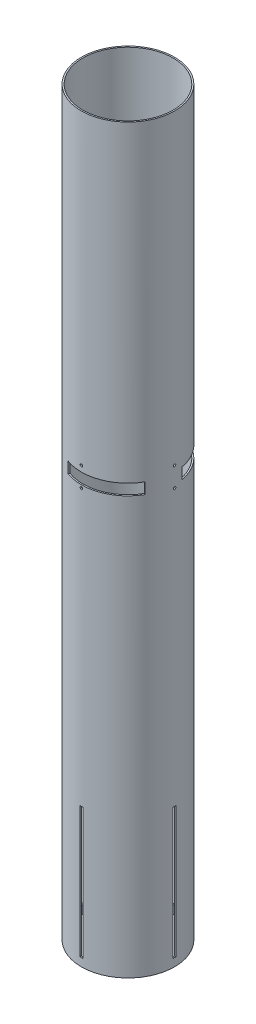
SolidWorks part; units mm, degrees
material "A-Glass Fiber"
ref_plane "Front Plane" through (0, 0, 0) normal (0, 0, 1) x (1, 0, 0)
ref_plane "Top Plane" through (0, 0, 0) normal (0, 1, 0) x (1, 0, 0)
ref_plane "Right Plane" through (0, 0, 0) normal (1, 0, 0) x (0, 0, -1)
sketch "Sketch1" plane through (0, 0, 0) normal (0, 1, 0) x (1, 0, 0)
  circle A0 centre (0, 0) radius 49.53
  circle A1 centre (0, 0) radius 51.1048
  dimension "D1" = 99.06
  dimension "D2" = 102.2096
extrude "Boss-Extrude1" add sketch "Sketch1" along normal blind 812.8
ref_plane "Plane1" through (0, 0, 0) normal (0.7071, 0, 0.7071) x (0.7071, 0, -0.7071)
ref_axis "Axis1" through (0, 812.8, 0) along (0, -1, 0)
sketch "Sketch2" plane through (0, 0, 0) normal (1, 0, 0) x (0, 0, -1)
  line L0 (0, 0) -> (0, 8.89)
  line L1 (1.5875, 8.89) -> (-1.5875, 8.89)
  line L2 (1.5875, 8.89) -> (1.5875, 152.4)
  line L3 (1.5875, 152.4) -> (-1.5875, 152.4)
  line L4 (-1.5875, 8.89) -> (-1.5875, 152.4)
  line L5 (1.5875, 8.89) -> (-1.5875, 152.4) construction
  line L6 (1.5875, 152.4) -> (-1.5875, 8.89) construction
  line L7 (51.1048, 812.8) -> (-51.1048, 812.8) construction
  line L8 (51.1048, 812.8) -> (-51.1048, 812.8)
  line L9 (0, 812.8) -> (0, 476.25)
  line L10 (-51.1048, 0) -> (51.1048, 0) construction
  circle A0 centre (0, 476.25) radius 1.3525
  point P0 (0, 80.645)
  dimension "D4" = 2.7051
  dimension "D1" = 3.175
  dimension "D5" = 476.25
  dimension "D3" = 152.4
  dimension "D2" = 8.89
extrude "Cut-Extrude1" cut sketch "Sketch2" against normal through all contours L4 L1 L2 L3 region at (0, 80.645, 0)
pattern_circular "CirPattern1" count 4 over 360 about axis through (0, 0, 0) along (0, 1, 0) of "Cut-Extrude1" reverse direction yes
extrude "Cut-Extrude2" cut sketch "Sketch2<3>" against normal through all contours A0 region at (0, 475.3207, 0.9293)
sketch "Sketch2<3>" plane through (0, 0, 0) normal (1, 0, 0) x (0, 0, -1) same geometry as "Sketch2"
pattern_circular "CirPattern2" count 4 over 360 about axis through (0, 812.8, 0) along (0, -1, 0) of "Cut-Extrude2"
sketch "Sketch3" plane through (0, 0, 0) normal (0.7071, 0, 0.7071) x (0.7071, 0, -0.7071)
  line L0 (0, 0) -> (0, 127) construction
  circle A0 centre (0, 127) radius 3.175
  dimension "D1" = 6.35
  dimension "D2" = 127
extrude "Cut-Extrude3" cut sketch "Sketch3" against normal through all
ref_plane "Plane3" through (0, 469.9, 0) normal (0, 1, 0) x (1, 0, 0)
sketch "Sketch7" plane through (0, 469.9, 0) normal (0, 1, 0) x (1, 0, 0)
  line L0 (0, 0) -> (-44.2581, -25.5524)
  line L1 (0, 0) -> (0, 93.232) construction
  line L2 (0, 0) -> (-32.8495, 39.1485)
  line L3 (-51.1048, 0) -> (0, 0) construction
  arc A0 (-51.0869, 1.3525) -> (-51.0869, -1.3525) centre (0, 0) ccw construction
  circle A1 centre (0, 0) radius 49.53 construction
  circle A2 centre (0, 0) radius 51.1048
  circle A3 centre (0, 0) radius 51.1048
  circle A4 centre (0, 0) radius 49.53
  circle A5 centre (0, 0) radius 51.1048 construction
  arc A6 (1.3526, 51.0869) -> (-1.3525, 51.0869) centre (0, 0) ccw construction
  arc A7 (-51.0869, 1.3525) -> (-51.0869, -1.3525) centre (0, 0) ccw
  arc A8 (1.3526, 51.0869) -> (-1.3525, 51.0869) centre (0, 0) ccw
  dimension "D1" = 80
  dimension "D3" = 30
  dimension "D2" = 0
extrude "Cut-Extrude4" cut sketch "Sketch7" against normal blind 12.065 contours A4 A3 L0 region at (-43.9137, 469.9, 24.5741)
pattern_circular "CirPattern3" count 3 over 360 about axis through (0, 812.8, 0) along (0, -1, 0) of "Cut-Extrude4"
pattern_linear "LPattern1" count 2 spacing 21.6916 along (0, -1, 0) of "CirPattern2"
equation "\"D1@Boss-Extrude1\" = \"Aft_Section_Length\""
equation "\"AB_Coupler_OD_Length\"= 1in"
equation "\"AB_Coupling_Section_Length\"= 0.375in"
equation "\"AB_Coupler_Length\"= \"AB_Coupler_OD_Length\" + \"AB_Coupling_Section_Length\" * 2"
equation "\"AB_Coupler_Num_Screws\"= 4"
equation "\"AB_Coupling_Screw_Diameter\"= 0.1065in"
equation "\"Aft_Section_Length\" = 32in"
equation "\"D4@Sketch2\"=\"AB_Coupling_Screw_Diameter\""
equation "\"D1@CirPattern2\"=\"AB_Coupler_Num_Screws\""
equation "\"Rail_Nut_From_Bottom\"= 5in"
equation "\"Rail_Nut_Diam\"= 0.25in"
equation "\"D1@Sketch3\"=\"Rail_Nut_Diam\""
equation "\"D2@Sketch3\"=\"Rail_Nut_From_Bottom\""
equation "\"AB_BKHD_Thickness\"= 0.375in"
equation "\"AB_Mount_From_Bottom\"= 18.75in"
equation "\"Cutout_Angle\" = 60"
equation "\"Motor_OD\" = 54.4mm"
equation "\"Motor_Length\" = 401mm"
equation "\"Mid_Coupler_Length\" = 12in"
equation "\"AB_Paddle_Height\" = 0.375in"
equation "\"Num_Cutouts\" = 4"
equation "\"AB_Coupler_OD\"= 4.024in"
equation "\"AB_Coupler_ID\"= 3.7in"
equation "\"AB_Coupler_Surface_Diameter\"= 3.899in"
equation "\"AB_Central_Bushing_Length\" = 0.75in"
equation "\"Lead_Screw_Dist\" = 2in"
equation "\"Lead_Screw_Diam\" = 0.375in"
equation "\"Lead_Screw_Length\" = \"Mid_Coupler_Length\" + 2*0.375in + 2*0.5in"
equation "\"Paddle_Pin_Offset\" = 0.25in"
equation "\"Paddle_Pin_Radius\" = 2.25*2/3in"
equation "\"Paddle_Gear_OD\" = 3.2in"
equation "\"Fwd_BKHD_From_Top\" = 18in"
equation "\"Body_Tube_OD\"= 4.024in"
equation "\"Body_Tube_ID\"= 3.90in"
equation "\"Coupler_OD\" = 3.899in"
equation "\"Coupler_ID\" = 3.755in"
equation "\"Fwd_Section_Length\" = 20in"
equation "\"Mid_Section_Length\" = 4in"
equation "\"Aft_Upper_Tube_Length\" = 10in"
equation "\"Aft_Lower_Tube_Length\" = 18in"
equation "\"Nosecone_Coupler_Length\" = 5in"
equation "\"Avionics_Bulkhead_Thickness\" = 0.25in"
equation "\"Avionics_Bulkhead_Lip\" = 0.125in"
equation "\"Avionics_Board_Length\" = \"Mid_Coupler_Length\" - 2*\"Avionics_Bulkhead_Lip\""
equation "\"Lead_Screw_Hole_Diam\" = 0.386in"
equation "\"Centering_Ring_Cutout_Dia\"=1.5in"
equation "\"D2@Sketch1\"=\"Body_Tube_OD\""
equation "\"D1@Sketch1\"=\"Body_Tube_ID\""
equation "\"D5@Sketch2\"=\"AB_Mount_From_Bottom\""
